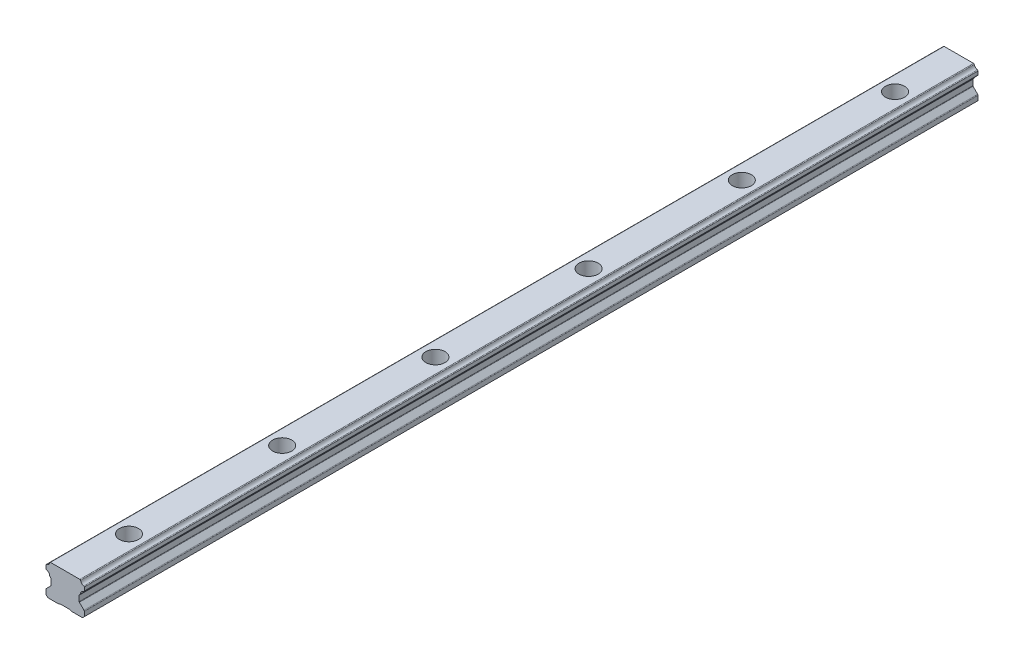
SolidWorks part; units mm, degrees
note: '?' marks a value the reader was unsure of.
ref_plane "Front Plane" through (0, 0, 0) normal (0, 0, 1) x (1, 0, 0)
ref_plane "Top Plane" through (0, 0, 0) normal (0, 1, 0) x (1, 0, 0)
ref_plane "Right Plane" through (0, 0, 0) normal (1, 0, 0) x (0, 0, -1)
ref_axis "Axis_X" through (-8.25, 0, 0) along (1, 0, 0)?
ref_axis "Axis_Y" through (0, 13.125, 0) along (0, -1, 0)?
ref_axis "Axis_Z" through (0, 0, -101.5) along (0, 0, 1)?
ref_plane "Plane1" through (0, 0, 25) normal (0, 0, 1) x (1, 0, 0)
sketch "Sketch1" plane through (0, 0, 25) normal (0, 0, 1) x (1, 0, 0)
  line L0 (-2.05, 0.3) -> (0, 0.3)
  line L1 (0, 0) -> (0, 12.5) construction
  line L2 (-2.05, 0.3) -> (-2.35, 0)
  line L3 (-2.35, 0) -> (-7.5, 0)
  line L5 (-7.5, 0) -> (-7.5, 2.7)
  line L6 (-7.5, 2.7) -> (-5.5, 4.7)
  line L7 (-5.5, 4.7) -> (-5.5, 7.1)
  line L8 (-5.5, 7.1) -> (-7.5, 7.1)
  line L9 (0, 12.5) -> (0, 0.3)
  line L14 (-7.5, 12.5) -> (-7.5, 7.1)
  line L29 (-7.5, 12.5) -> (0, 12.5)
  dimension "KSS_1" = 0.3
  dimension "MSM_3" = 2.7
  dimension "FIX_1" = 45
  dimension "MSM_4" = 7.1
  dimension "MSM_2" = 4.1
  dimension "WR" = 15
  dimension "HR" = 12.5
  dimension "MSM_1" = 11
extrude "Boss-Extrude101" add sketch "Sketch1" against normal blind 350
sketch "Sketch2" plane through (0, 0, 25) normal (0, 0, 1) x (1, 0, 0)
  line L0 (0, 0) -> (0, 12.5) construction
  line L1 (-7.5, 0) -> (-2.35, 0) construction
  line L2 (-5.5, 7.1) -> (-6.0305, 7.6305)
  line L3 (-5.5, 4.7) -> (-7.5, 2.7) construction
  line L4 (-5.5, 7.1) -> (-5.5, 4.7)
  line L5 (-5.5, 4.7) -> (-7.5, 2.7)
  line L6 (-7.5, 2.7) -> (-7.53, 6.17)
  circle A0 centre (-7.53, 12.53) radius 1.5
  arc A1 (-6.0305, 7.6305) -> (-7.53, 6.17) centre (-7.53, 7.67) ccw
  dimension "MSM_5" = 3
  dimension "MSM_6" = 15.06
  dimension "MSM_7" = 4.86
  dimension "MSM_8" = 7.67
extrude "Cut-Extrude101" cut sketch "Sketch2" against normal through all
chamfer "Chamfer101" distance 0.7 1 edges at (-7.5, 0, -150)
fillet "Fillet101" radius 0.5 1 edges at (-7.5, 2.7, -150)
fillet "Fillet102" radius 0.3 1 edges at (-5.5, 7.1, -150)
fillet "Fillet103" radius 0.3 3 edges at (-7.5, 9.1697, -150) (-7.5, 11.0303, -150) (-6.0303, 12.5, -150)
fillet "Fillet104" radius 0.3 1 edges at (-5.5, 4.7, -150)
mirror "Mirror101" about plane through (0, 0, 0) normal (1, 0, 0) of "Fillet104", "Fillet103", "Fillet102", "Fillet101", "Chamfer101", "Cut-Extrude101", "Boss-Extrude101"
hole_wizard "CBORE101" positions "Sketch4" profile "Sketch3" counterbore size "M5" standard "JIS" end condition through all
sketch "Sketch4" plane through (0, 12.5, 0) normal (0, 1, 0) x (1, 0, 0)
  point P0 (0, 0)
sketch "Sketch3" plane through (0, 12.5, 0) normal (1, 0, 0) x (0, 0, 1)
  line L0 (0, 0) -> (0, 12.5)
  line L1 (0, 12.5) -> (2.25, 12.5)
  line L3 (2.25, 12.5) -> (2.25, 5.3)
  line L4 (2.25, 5.3) -> (3.75, 5.3)
  line L5 (3.75, 5.3) -> (3.75, 0)
  line L7 (3.75, 0) -> (0, 0)
  line L11 (0, -6.35) -> (0, 107.95) construction
  dimension "D_s" = 4.5
  dimension "Thru Hole Depth" = 12.5
  dimension "D" = 7.5
  dimension "H_s" = 5.3
pattern_linear "LPattern101" count 6 spacing 60 along (0, 0, -1) of "CBORE101"
hole_wizard "CBORE102" [suppressed] positions "Sketch6" profile "Sketch5" counterbore size "M5" standard "JIS"
sketch "Sketch6" [suppressed] plane through (0, 12.5, 0) normal (0, 1, 0) x (1, 0, 0)
  line L0 (5.7605, -20) -> (-5.7605, -20) construction
  point P0 (0, -19)
  dimension "ES" = 2
sketch "Sketch5" [suppressed] plane through (0, 12.5, 19) normal (1, 0, 0) x (0, 0, 1)
  line L0 (0, 0) -> (0, 12.5)
  line L1 (0, 12.5) -> (2.25, 12.5)
  line L3 (2.25, 12.5) -> (2.25, 5.3)
  line L4 (2.25, 5.3) -> (3.75, 5.3)
  line L5 (3.75, 5.3) -> (3.75, 0)
  line L7 (3.75, 0) -> (0, 0)
  line L11 (0, -6.35) -> (0, 107.95) construction
  dimension "D_s" = 4.5
  dimension "Thru Hole Depth" = 12.5
  dimension "D" = 7.5
  dimension "H_s" = 5.3
pattern_linear "LPattern102" [suppressed]
hole_wizard "CBORE103" [suppressed] positions "Sketch8" profile "Sketch7" counterbore size "M5" standard "JIS"
sketch "Sketch8" [suppressed] plane through (0, 12.5, 0) normal (0, 1, 0) x (1, 0, 0)
  line L0 (5.7605, 80) -> (-5.7605, 80) construction
  point P0 (0, 79)
  dimension "EB" = 2
sketch "Sketch7" [suppressed] plane through (0, 12.5, -79) normal (1, 0, 0) x (0, 0, 1)
  line L0 (0, 0) -> (0, 12.5)
  line L1 (0, 12.5) -> (2.25, 12.5)
  line L3 (2.25, 12.5) -> (2.25, 5.3)
  line L4 (2.25, 5.3) -> (3.75, 5.3)
  line L5 (3.75, 5.3) -> (3.75, 0)
  line L7 (3.75, 0) -> (0, 0)
  line L11 (0, -6.35) -> (0, 107.95) construction
  dimension "D_s" = 4.5
  dimension "Thru Hole Depth" = 12.5
  dimension "D" = 7.5
  dimension "H_s" = 5.3
pattern_linear "LPattern103" [suppressed]
equation "\"Factor\"= 1.082532"
equation "\"L\"=350"
equation "\"M_2\"=6"
equation "\"P\"=60"
equation "\"E@Plane1\" = ( \"L\" - ( ( \"M_2\" - 1 ) * \"P\" ) ) / 2"
equation "\"KSS_1@Sketch1\"= if ( \"WR@Sketch1\" = 15 , 0.3 , 0.5 )"
equation "\"KSS_2@Fillet101\"= if ( \"WR@Sketch1\" = 15 , 0.5 , 1.5 )"
equation "\"ES\"= 2"
equation "\"EB\"= 2"
equation "\"ES@Sketch6\"= iif ( \"ES\" > 2 * \"E@Plane1\" , 2 * \"E@Plane1\" , \"ES\" )"
equation "\"EB@Sketch8\"= iif ( \"EB\" > 2 * \"E@Plane1\" , 2 * \"E@Plane1\" , \"EB\" )"
